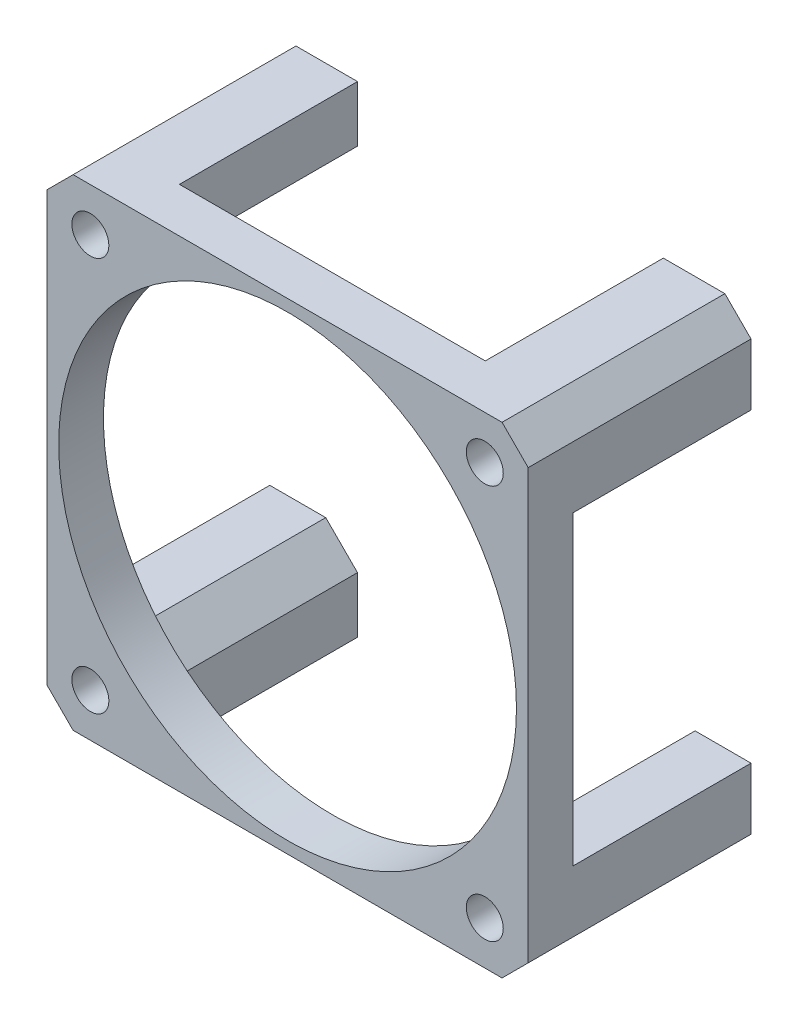
SolidWorks part; units mm, degrees
ref_plane "Front Plane" through (0, 0, 0) normal (0, 0, 1) x (1, 0, 0)
ref_plane "Top Plane" through (0, 0, 0) normal (0, 1, 0) x (1, 0, 0)
ref_plane "Right Plane" through (0, 0, 0) normal (1, 0, 0) x (0, 0, -1)
sketch "Sketch1" plane through (0, 0, 0) normal (0, 0, 1) x (1, 0, 0)
  line L0 (19.1622, -21.5) -> (21.5, -19.1622)
  line L1 (21.5, -19.1622) -> (21.5, 19.1622)
  line L2 (21.5, 19.1622) -> (19.1622, 21.5)
  line L3 (19.1622, 21.5) -> (-19.1622, 21.5)
  line L4 (-19.1622, 21.5) -> (-21.5, 19.1622)
  line L5 (-21.5, 19.1622) -> (-21.5, -19.1622)
  line L6 (-21.5, -19.1622) -> (-19.1622, -21.5)
  line L7 (-19.1622, -21.5) -> (19.1622, -21.5)
  line L8 (-17.6212, 17.6212) -> (17.6212, 17.6212) construction
  line L9 (17.6212, 17.6212) -> (17.6212, -17.6212) construction
  line L10 (17.6212, -17.6212) -> (-17.6212, -17.6212) construction
  line L11 (-17.6212, -17.6212) -> (-17.6212, 17.6212) construction
  line L12 (-19.1622, -21.5) -> (-13.6622, -21.5)
  line L13 (-21.5, -19.1622) -> (-21.5, -13.6622)
  line L14 (-21.5, -13.6622) -> (21.5, -13.6622) construction
  line L15 (19.1622, -21.5) -> (13.6622, -21.5)
  line L16 (-21.5, -13.6622) -> (-16.5, -13.6622)
  line L17 (-13.6622, -21.5) -> (-13.6622, -16.5)
  line L18 (-13.6622, -16.5) -> (-16.5, -13.6622)
  line L19 (13.6622, -21.5) -> (13.6622, -16.5)
  line L20 (21.5, -13.6622) -> (16.5, -13.6622)
  line L21 (13.6622, -16.5) -> (16.5, -13.6622)
  line L22 (13.6622, -16.5) -> (13.6622, 21.5) construction
  line L23 (13.6622, 21.5) -> (13.6622, 16.5)
  line L24 (21.5, 19.1622) -> (21.5, 13.6622)
  line L25 (21.5, 13.6622) -> (16.5, 13.6622)
  line L26 (16.5, 13.6622) -> (13.6622, 16.5)
  line L27 (-21.5, 13.6622) -> (-16.5, 13.6622)
  line L28 (-16.5, 13.6622) -> (-13.6622, 16.5)
  line L29 (-13.6622, 16.5) -> (-13.6622, 21.5)
  circle A4 centre (17.6212, -17.6212) radius 1.65
  circle A5 centre (-17.6212, -17.6212) radius 1.6501
  circle A6 centre (-17.6212, 17.6212) radius 1.65
  circle A7 centre (17.6212, 17.6212) radius 1.65
  circle A8 centre (0, 0) radius 20.45
extrude "Boss-Extrude1" add sketch "Sketch1" along normal blind 4 contours L29 L28 L27 L5 L16 L18 L17 L7 L19 L21 L20 L1 L25 L26 L23 L3 A8 | L21 L19 L7 L0 L1 L20 A4 | L17 L18 L16 L5 L6 L7 A5 | L28 L29 L3 L4 L5 L27 A6 | L26 L25 L1 L2 L3 L23 A7 region at (16.4122, -21.3892, 0) region at (0, -20.8919, 0) region at (-16.4122, -21.3892, 0) region at (19, 13.773, 0) region at (-21.3892, 16.4122, 0)
extrude "Boss-Extrude2" add sketch "Sketch1<4>" against normal blind 15.91 contours L21 L19 L7 L0 L1 L20 A4 | L26 L25 L1 L2 L3 L23 A7 | L28 L29 L3 L4 L5 L27 A6 | L17 L18 L16 L5 L6 L7 A5 region at (16.4122, -21.3892, 0) region at (-16.4122, -21.3892, 0) region at (19, 13.773, 0) region at (-21.3892, 16.4122, 0)
sketch "Sketch1<4>" plane through (0, 0, 0) normal (0, 0, 1) x (1, 0, 0) same geometry as "Sketch1"
